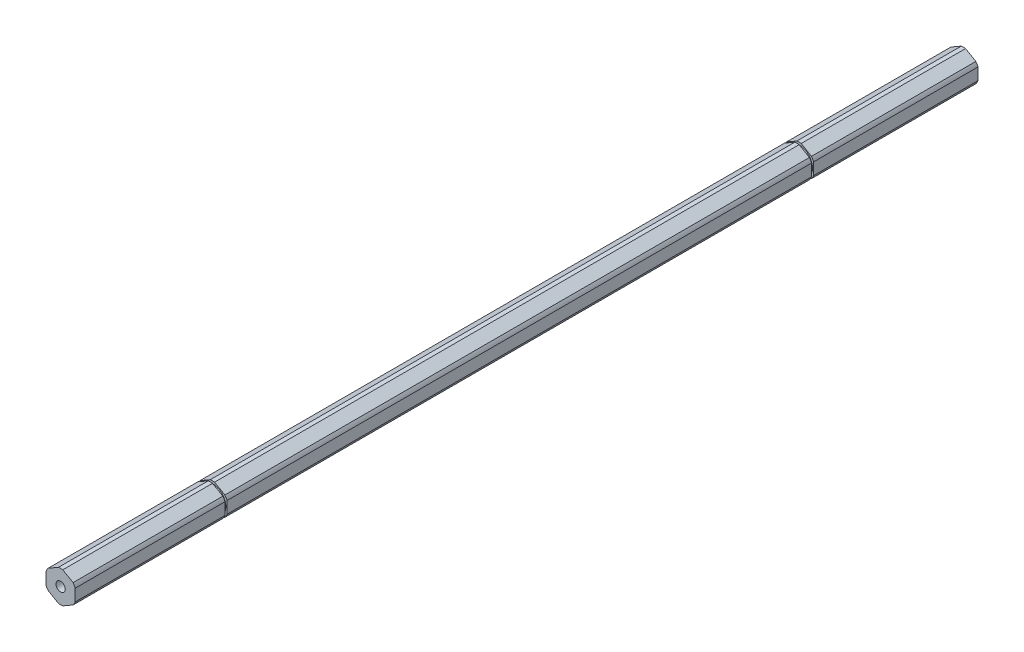
SolidWorks part; units mm, degrees
material "6061-T6 (SS)"
ref_plane "Front Plane" through (0, 0, 0) normal (0, 0, 1) x (1, 0, 0)
ref_plane "Top Plane" through (0, 0, 0) normal (0, 1, 0) x (1, 0, 0)
ref_plane "Right Plane" through (0, 0, 0) normal (1, 0, 0) x (0, 0, -1)
sketch "Sketch1" plane through (0, 0, 0) normal (0, 0, 1) x (1, 0, 0)
  line L1 (0, 7.3323) -> (-6.35, 3.6662)
  line L2 (-6.35, 3.6662) -> (-6.35, -3.6662)
  line L3 (-6.35, -3.6662) -> (0, -7.3323)
  line L4 (0, -7.3323) -> (6.35, -3.6662)
  line L5 (6.35, -3.6662) -> (6.35, 3.6662)
  line L6 (6.35, 3.6662) -> (0, 7.3323)
  circle A0 centre (0, 0) radius 6.35 construction
  circle A1 centre (0, 0) radius 6.858
  dimension "D1" = 12.7
  dimension "D2" = 13.716
extrude "Boss-Extrude1" add sketch "Sketch1" along normal mid plane 392.303 contours L5 A1 L6 L1 L2 L3 L4 region at (0, 0, 0)
sketch "Sketch2" plane through (0, 0, 196.1515) normal (0, 0, 1) x (1, 0, 0)
  circle A0 centre (0, 0) radius 2.0193
  dimension "D1" = 4.0386
extrude "Cut-Extrude1" cut sketch "Sketch2" against normal through all
sketch "Sketch4" plane through (0, 0, 0) normal (0, 1, 0) x (1, 0, 0)
  line L0 (-2.0193, -196.1515) -> (2.0193, -196.1515) construction
  line L5 (-0.9317, -196.1515) -> (0.9317, -196.1515) construction
  line L7 (9.0297, 124.7267) -> (5.8547, 124.7267)
  line L8 (9.0297, 124.7267) -> (9.0297, 123.8377)
  line L9 (9.0297, 123.8377) -> (5.8547, 123.8377)
  line L10 (5.8547, 124.7267) -> (5.8547, 123.8377)
  line L11 (5.8547, -131.0767) -> (9.0297, -131.0767)
  line L12 (0, 196.1515) -> (0, -196.1515) construction
  line L13 (2.0193, 196.1515) -> (-2.0193, 196.1515) construction
  line L14 (5.8547, -131.0767) -> (5.8547, -130.1877)
  line L15 (5.8547, -130.1877) -> (9.0297, -130.1877)
  line L16 (9.0297, -131.0767) -> (9.0297, -130.1877)
  point P16 (5.8517, -130.1877)
  dimension "D1" = 0.889
  dimension "D2" = 392.303
  dimension "D3" = 5.8547
  dimension "D4" = 71.4248
  dimension "D5" = 3.175
  dimension "D6" = 3.175
  dimension "D7" = 0.889
  dimension "D8" = 65.0748
revolve "Cut-Revolve4" cut sketch "Sketch4" angle 360 about L12
